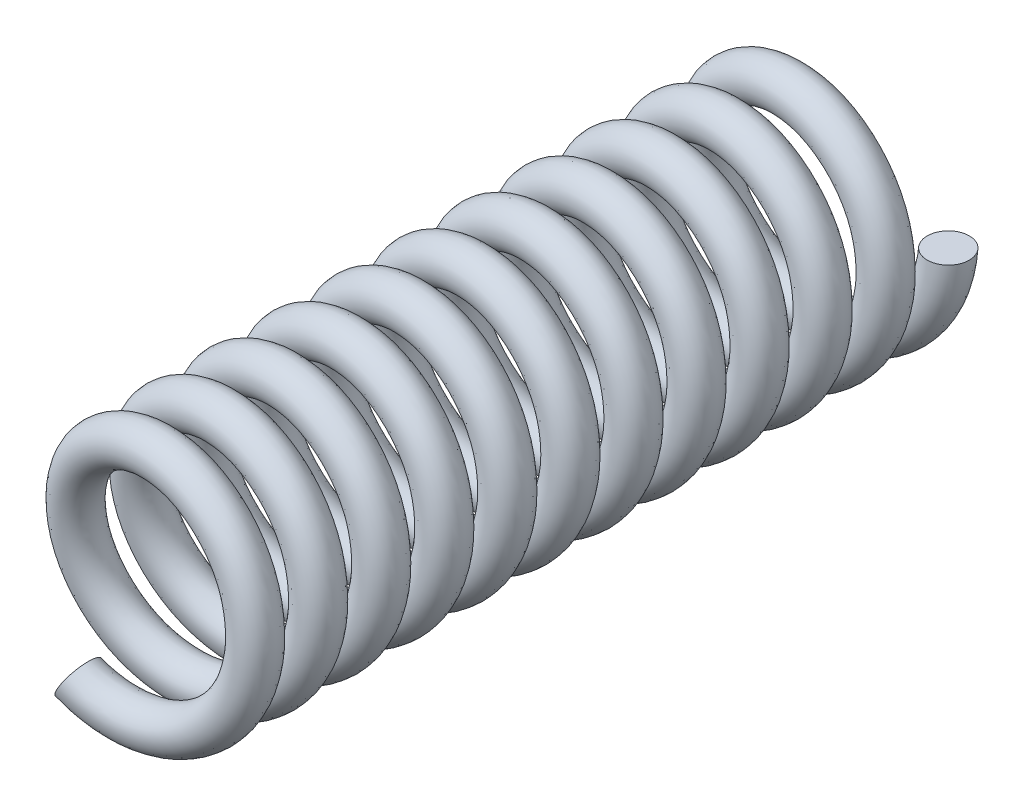
SolidWorks part; units mm, degrees
ref_plane "Front Plane" through (0, 0, 0) normal (0, 0, 1) x (1, 0, 0)
ref_plane "Top Plane" through (0, 0, 0) normal (0, 1, 0) x (1, 0, 0)
ref_plane "Right Plane" through (0, 0, 0) normal (1, 0, 0) x (0, 0, -1)
sketch "Sketch1" plane through (0, 0, 0) normal (0, 0, 1) x (1, 0, 0)
  circle A0 centre (0, 0) radius 2.5
  dimension "D1" = 5
curve "Helix/Spiral1" pitch 1.5 height 16.995 turns 11.33
sketch "Sketch2" plane through (0, 0, 0) normal (0, 1, 0) x (1, 0, 0)
  circle A0 centre (2.5, 0) radius 0.5
  spline S0 degree 3 poles (2.5, 0) (2.5, -0.0311) (2.3694, -0.094) (1.8117, -0.1878) (0.9774, -0.2817) (-0.0062, -0.3756) (-0.9889, -0.4695) (-1.8205, -0.5634) (-2.3742, -0.6573) (-2.5653, -0.7512) (-2.3646, -0.8451) (-1.8029, -0.939) (-0.9658, -1.0328) (0.0187, -1.1267) (1.0004, -1.2206) (1.8293, -1.3145) (2.3789, -1.4084) (2.5652, -1.5023) (2.3598, -1.5962) (1.794, -1.6901) (0.9543, -1.784) (-0.0312, -1.8779) (-1.0118, -1.9718) (-1.838, -2.0657) (-2.3835, -2.1596) (-2.565, -2.2535) (-2.3548, -2.3474) (-1.7851, -2.4413) (-0.9427, -2.5352) (0.0436, -2.6291) (1.0233, -2.723) (1.8467, -2.8169) (2.3881, -2.9107) (2.5648, -3.0046) (2.3499, -3.0985) (1.7761, -3.1924) (0.9311, -3.2863) (-0.0561, -3.3802) (-1.0347, -3.4741) (-1.8553, -3.568) (-2.3926, -3.6619) (-2.5645, -3.7558) (-2.3448, -3.8497) (-1.7671, -3.9436) (-0.9195, -4.0375) (0.0686, -4.1314) (1.0461, -4.2253) (1.8639, -4.3192) (2.3971, -4.4131) (2.5642, -4.507) (2.3398, -4.6009) (1.758, -4.6948) (0.9078, -4.7886) (-0.081, -4.8825) (-1.0575, -4.9764) (-1.8725, -5.0703) (-2.4015, -5.1642) (-2.5638, -5.2581) (-2.3346, -5.352) (-1.7489, -5.4459) (-0.8961, -5.5398) (0.0935, -5.6337) (1.0688, -5.7276) (1.881, -5.8215) (2.4058, -5.9154) (2.5634, -6.0093) (2.3294, -6.1032) (1.7398, -6.1971) (0.8844, -6.291) (-0.1059, -6.3849) (-1.0801, -6.4788) (-1.8894, -6.5727) (-2.4101, -6.6665) (-2.5628, -6.7604) (-2.3242, -6.8543) (-1.7306, -6.9482) (-0.8727, -7.0421) (0.1184, -7.136) (1.0914, -7.2299) (1.8978, -7.3238) (2.4144, -7.4177) (2.5623, -7.5116) (2.3189, -7.6055) (1.7214, -7.6994) (0.861, -7.7933) (-0.1308, -7.8872) (-1.1027, -7.9811) (-1.9062, -8.075) (-2.4186, -8.1689) (-2.5616, -8.2628) (-2.3135, -8.3567) (-1.7121, -8.4506) (-0.8492, -8.5444) (0.1433, -8.6383) (1.114, -8.7322) (1.9145, -8.8261) (2.4227, -8.92) (2.5609, -9.0139) (2.3081, -9.1078) (1.7028, -9.2017) (0.8375, -9.2956) (-0.1557, -9.3895) (-1.1252, -9.4834) (-1.9228, -9.5773) (-2.4268, -9.6712) (-2.5602, -9.7651) (-2.3026, -9.859) (-1.6934, -9.9529) (-0.8257, -10.0468) (0.1682, -10.1407) (1.1364, -10.2346) (1.931, -10.3285) (2.4308, -10.4223) (2.5594, -10.5162) (2.2971, -10.6101) (1.6841, -10.704) (0.8139, -10.7979) (-0.1806, -10.8918) (-1.1475, -10.9857) (-1.9392, -11.0796) (-2.4347, -11.1735) (-2.5585, -11.2674) (-2.2915, -11.3613) (-1.6746, -11.4552) (-0.802, -11.5491) (0.1931, -11.643) (1.1587, -11.7369) (1.9473, -11.8308) (2.4386, -11.9247) (2.5575, -12.0186) (2.2859, -12.1125) (1.6652, -12.2064) (0.7902, -12.3002) (-0.2055, -12.3941) (-1.1698, -12.488) (-1.9554, -12.5819) (-2.4425, -12.6758) (-2.5565, -12.7697) (-2.2802, -12.8636) (-1.6557, -12.9575) (-0.7783, -13.0514) (0.2179, -13.1453) (1.1809, -13.2392) (1.9635, -13.3331) (2.4463, -13.427) (2.5555, -13.5209) (2.2745, -13.6148) (1.6461, -13.7087) (0.7664, -13.8026) (-0.2303, -13.8965) (-1.1919, -13.9904) (-1.9715, -14.0843) (-2.45, -14.1781) (-2.5544, -14.272) (-2.2687, -14.3659) (-1.6365, -14.4598) (-0.7545, -14.5537) (0.2427, -14.6476) (1.2029, -14.7415) (1.9794, -14.8354) (2.4536, -14.9293) (2.5532, -15.0232) (2.2628, -15.1171) (1.6269, -15.211) (0.7426, -15.3049) (-0.2552, -15.3988) (-1.2139, -15.4927) (-1.9873, -15.5866) (-2.4573, -15.6805) (-2.5519, -15.7744) (-2.2569, -15.8683) (-1.6173, -15.9622) (-0.7306, -16.056) (0.2676, -16.1499) (1.2249, -16.2438) (1.9952, -16.3377) (2.4608, -16.4316) (2.5506, -16.5255) (2.251, -16.6194) (1.6076, -16.7133) (0.7185, -16.8072) (-0.2791, -16.901) (-0.919, -16.9639) (-1.2044, -16.995) knots 0 0 0 0 0.005525 0.01105 0.016575 0.022099 0.027624 0.033149 0.038674 0.044199 0.049724 0.055249 0.060773 0.066298 0.071823 0.077348 0.082873 0.088398 0.093923 0.099448 0.104972 0.110497 0.116022 0.121547 0.127072 0.132597 0.138122 0.143646 0.149171 0.154696 0.160221 0.165746 0.171271 0.176796 0.18232 0.187845 0.19337 0.198895 0.20442 0.209945 0.21547 0.220994 0.226519 0.232044 0.237569 0.243094 0.248619 0.254144 0.259669 0.265193 0.270718 0.276243 0.281768 0.287293 0.292818 0.298343 0.303867 0.309392 0.314917 0.320442 0.325967 0.331492 0.337017 0.342541 0.348066 0.353591 0.359116 0.364641 0.370166 0.375691 0.381215 0.38674 0.392265 0.39779 0.403315 0.40884 0.414365 0.41989 0.425414 0.430939 0.436464 0.441989 0.447514 0.453039 0.458564 0.464088 0.469613 0.475138 0.480663 0.486188 0.491713 0.497238 0.502762 0.508287 0.513812 0.519337 0.524862 0.530387 0.535912 0.541436 0.546961 0.552486 0.558011 0.563536 0.569061 0.574586 0.58011 0.585635 0.59116 0.596685 0.60221 0.607735 0.61326 0.618785 0.624309 0.629834 0.635359 0.640884 0.646409 0.651934 0.657459 0.662983 0.668508 0.674033 0.679558 0.685083 0.690608 0.696133 0.701657 0.707182 0.712707 0.718232 0.723757 0.729282 0.734807 0.740331 0.745856 0.751381 0.756906 0.762431 0.767956 0.773481 0.779006 0.78453 0.790055 0.79558 0.801105 0.80663 0.812155 0.81768 0.823204 0.828729 0.834254 0.839779 0.845304 0.850829 0.856354 0.861878 0.867403 0.872928 0.878453 0.883978 0.889503 0.895028 0.900552 0.906077 0.911602 0.917127 0.922652 0.928177 0.933702 0.939227 0.944751 0.950276 0.955801 0.961326 0.966851 0.972376 0.977901 0.983425 0.98895 0.994475 1 1 1 1 construction
  dimension "D1" = 1
sweep "Sweep1" add profiles "Sketch2" path "Helix/Spiral1"
